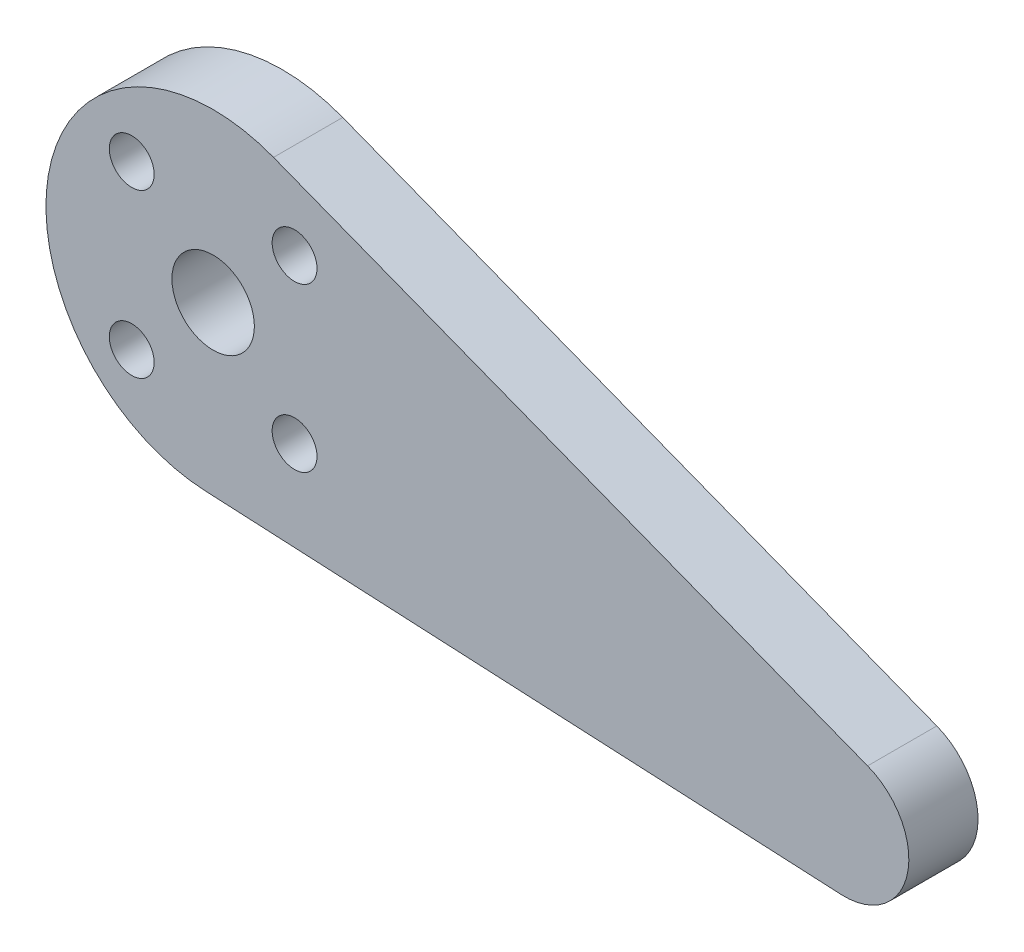
SolidWorks part; units mm, degrees
ref_plane "Front Plane" through (0, 0, 0) normal (0, 0, 1) x (1, 0, 0)
ref_plane "Top Plane" through (0, 0, 0) normal (0, 1, 0) x (1, 0, 0)
ref_plane "Right Plane" through (0, 0, 0) normal (1, 0, 0) x (0, 0, -1)
ref_plane "Plane1" through (0, 0, 0) normal (0, 0, -1) x (-1, 0, 0)
sketch "Sketch1" plane through (0, 0, 0) normal (0, 0, -1) x (-1, 0, 0)
  line L0 (-54.9006, 0.2614) -> (-46.1167, 9.6815) construction
  line L1 (-54.6285, -5.2121) -> (-0.5934, -2.5259)
  line L3 (-54.9006, 0.2614) -> (-1.2984, 11.6566) construction
  line L4 (-8.3993, 23.9536) -> (-43.781, 5.2606)
  line L5 (-46.7655, 4.7237) -> (-54.1894, 5.6953)
  circle A0 centre (-46.1167, 9.6815) radius 4 construction
  arc A2 (-54.1894, 5.6953) -> (-54.6285, -5.2121) centre (-54.9006, 0.2614) ccw
  arc A3 (-0.5934, -2.5259) -> (-8.3993, 23.9536) centre (-1.2984, 11.6566) ccw
  arc A4 (-46.7655, 4.7237) -> (-43.781, 5.2606) centre (-46.1167, 9.6815) ccw
  dimension "D2" = 14.2
  dimension "D3" = 12.88
  dimension "D5" = 35
  dimension "D6" = 8
  dimension "D7" = 10
  dimension "D1" = 54.8
extrude "Boss-Extrude1" add sketch "Sketch1" against normal blind 15
sketch "Sketch10" plane through (0, 0, 0) normal (0, 0, -1) x (-1, 0, 0)
  circle A0 centre (-1.2984, 11.6566) radius 14.2
  arc A1 (-0.5934, -2.5259) -> (-8.3993, 23.9536) centre (-1.2984, 11.6566) ccw construction
  circle A2 centre (-54.9006, 0.2614) radius 5.4803
  arc A3 (-54.1894, 5.6953) -> (-54.6285, -5.2121) centre (-54.9006, 0.2614) ccw construction
  point P5 (-1.2984, 11.6566)
hole_wizard "CBORE for M6 Hex Head Bolt1" positions "Sketch7" profile "Sketch6" counterbore size "M6" standard "Ansi Metric" end condition through all
sketch "Sketch7" plane through (0, 0, 0) normal (0, 0, -1) x (-1, 0, 0)
  point P0 (-1.2984, 11.6566)
sketch "Sketch6" plane through (1.2984, 11.6566, 0) normal (1, 0, 0) x (0, 1, 0)
  line L0 (0, 0) -> (0, 15)
  line L1 (0, 15) -> (3.5, 15)
  line L3 (3.5, 15) -> (3.5, 3)
  line L4 (3.5, 3) -> (12.8, 3)
  line L5 (12.8, 3) -> (12.8, 0)
  line L7 (12.8, 0) -> (0, 0)
  line L11 (0, -6.35) -> (0, 107.95) construction
  dimension "Thru Hole Dia." = 7
  dimension "Thru Hole Depth" = 15
  dimension "C'Bore Dia." = 25.6
  dimension "C'Bore Depth" = 3
ref_plane "Plane4" through (0, 0, 7.5) normal (0, 0, -1) x (-1, 0, 0)
sketch "Sketch30" plane through (0, 0, 15) normal (0, 0, 1) x (1, 0, 0)
  line L1 (68.7065, -22.2417) -> (-19.1857, -22.2417)
  line L2 (68.7065, -22.2417) -> (68.7065, 41.145)
  line L3 (68.7065, 41.145) -> (-19.1857, 41.145)
  line L4 (-19.1857, -22.2417) -> (-19.1857, 41.145)
extrude "Cut-Extrude8" cut sketch "Sketch30" against normal blind 0.125
sketch "Sketch31" plane through (0, 0, 0) normal (0, 0, -1) x (-1, 0, 0)
  line L1 (-64.611, 30.1264) -> (17.734, 30.1264)
  line L2 (-64.611, 30.1264) -> (-64.611, -8.8981)
  line L3 (-64.611, -8.8981) -> (17.734, -8.8981)
  line L4 (17.734, 30.1264) -> (17.734, -8.8981)
extrude "Cut-Extrude9" cut sketch "Sketch31" against normal blind 0.125
sketch "Sketch38" plane through (0, 0, 14.875) normal (0, 0, 1) x (1, 0, 0)
  circle A0 centre (1.2984, 11.6566) radius 3.5 construction
  circle A1 centre (1.2984, 11.6566) radius 3.5
  circle A2 centre (-5.616, 18.5718) radius 1.905
  circle A3 centre (8.2136, 18.571) radius 1.905
  circle A4 centre (8.2128, 4.7414) radius 1.905
  circle A5 centre (-5.6168, 4.7422) radius 1.905
  line B0 (3.7785, 13.3445) -> (3.7783, 9.9684)
  line B1 (-14.7035, 12.2926) -> (-1.6336, 12.2918)
  line B2 (-14.7033, 16.4201) -> (-14.7035, 12.2926)
  line B3 (-11.9069, 16.4199) -> (-14.7033, 16.4201)
  line B4 (-11.2749, 6.8948) -> (-11.2749, 6.8267)
  line B5 (-14.7039, 6.8951) -> (-11.2749, 6.8948)
  line B6 (-14.7036, 11.0226) -> (-14.7039, 6.8951)
  line B7 (-1.6336, 11.0218) -> (-14.7036, 11.0226)
  arc B8 (2.6475, 8.977) -> (3.7783, 9.9684) centre (2.7783, 9.9684) ccw
  arc B9 (3.7785, 13.3445) -> (2.6478, 14.336) centre (2.7785, 13.3446) ccw
  arc B10 (2.6478, 14.336) -> (-1.6336, 12.2918) centre (1.2984, 11.6566) ccw
  arc B11 (-11.9069, 16.4199) -> (-8.9599, 19.0076) centre (-11.9068, 19.3917) ccw
  arc B12 (-4.0299, 21.5478) -> (-8.9599, 19.0076) centre (-5.616, 18.5718) ccw
  arc B13 (-4.0299, 21.5478) -> (-1.7731, 21.3412) centre (-2.6561, 24.1255) ccw
  arc B14 (4.3711, 21.3408) -> (-1.7731, 21.3412) centre (1.2984, 11.6566) ccw
  arc B15 (4.3711, 21.3408) -> (6.628, 21.5471) centre (5.2545, 24.1251) ccw
  arc B16 (11.1896, 16.985) -> (6.628, 21.5471) centre (8.2136, 18.571) ccw
  arc B17 (11.1896, 16.985) -> (10.983, 14.7281) centre (13.7674, 15.6111) ccw
  arc B18 (10.9827, 8.5839) -> (10.983, 14.7281) centre (1.2984, 11.6566) ccw
  arc B19 (10.9827, 8.5839) -> (11.189, 6.3271) centre (13.7669, 7.7006) ccw
  arc B20 (6.6268, 1.7654) -> (11.189, 6.3271) centre (8.2128, 4.7414) ccw
  arc B21 (6.6268, 1.7654) -> (4.3699, 1.972) centre (5.253, -0.8123) ccw
  arc B22 (-1.7742, 1.9724) -> (4.3699, 1.972) centre (1.2984, 11.6566) ccw
  arc B23 (-1.7742, 1.9724) -> (-4.0311, 1.7661) centre (-2.6576, -0.8119) ccw
  arc B24 (-8.9608, 4.3068) -> (-4.0311, 1.7661) centre (-5.6168, 4.7422) ccw
  arc B25 (-8.9608, 4.3068) -> (-11.2749, 6.8267) centre (-11.9077, 3.9231) ccw
  arc B26 (-1.6336, 11.0218) -> (2.6475, 8.977) centre (1.2984, 11.6566) ccw
  dimension "D1" = 3.81
sketch_block_instance "Block1-1"
sketch_block "Block1"
extrude "Cut-Extrude10" cut sketch "Sketch38" against normal through all contours A2 | A3 | A4 | A5
sketch "Sketch39" plane through (0, 0, 0.125) normal (0, 0, -1) x (-1, 0, 0)
  circle A1 centre (-1.2984, 11.6566) radius 12.8 construction
  circle A2 centre (-1.2984, 11.6566) radius 12.8
extrude "Cut-Extrude11" cut sketch "Sketch39" against normal offset from surface (7.75 mm away) 7 flip side to cut contours A2 up to face at (-3.7118, 4.7422, 14.875)
sketch "Sketch40" plane through (0, 0, 14.875) normal (0, 0, 1) x (1, 0, 0)
  circle A0 centre (1.2984, 11.6566) radius 13
  dimension "D1" = 26
extrude "Cut-Extrude12" cut sketch "Sketch40" against normal offset from surface (6 mm away) 1 up to face at (32.9108, 6.1436, 7.875)
sketch "Sketch42" plane through (0, 0, 14.875) normal (0, 0, 1) x (1, 0, 0)
  line L0 (6.4237, 24.8994) -> (56.8786, 5.3722)
  line L3 (43.781, 5.2606) -> (8.3993, 23.9536)
  line L4 (0.5934, -2.5259) -> (54.6285, -5.2121)
  line L5 (54.1894, 5.6953) -> (46.7655, 4.7237)
  line L6 (43.781, 5.2606) -> (8.3993, 23.9536)
  line L8 (54.1894, 5.6953) -> (46.7655, 4.7237)
  arc A0 (54.6285, -5.2121) -> (54.1894, 5.6953) centre (54.9006, 0.2614) ccw construction
  arc A3 (8.3993, 23.9536) -> (0.5934, -2.5259) centre (1.2984, 11.6566) ccw
  arc A4 (54.6285, -5.2121) -> (54.1894, 5.6953) centre (54.9006, 0.2614) ccw
  arc A5 (43.781, 5.2606) -> (46.7655, 4.7237) centre (46.1167, 9.6815) ccw
  arc A6 (8.3993, 23.9536) -> (6.4237, 24.8994) centre (1.2984, 11.6566) ccw
  arc A7 (56.8786, 5.3722) -> (54.1894, 5.6953) centre (54.9006, 0.2614) ccw
  arc A8 (43.781, 5.2606) -> (46.7655, 4.7237) centre (46.1167, 9.6815) ccw
  point P10 (57.2562, 5.2095)
  point P12 (6.2267, 24.9756)
  point P13 (2.733, 26.3278)
  point P14 (56.8786, 5.3722)
  point P18 (56.8786, 5.2606)
  point P19 (56.8786, 5.3722)
  dimension "D1" = 0
extrude "Boss-Extrude2" add sketch "Sketch42" against normal up to surface (7 mm away) up to face at (32.9108, 6.1436, 7.875)
sketch "Sketch43" plane through (0, 0, 7.875) normal (0, 0, -1) x (-1, 0, 0)
  line L2 (-6.4237, 24.8994) -> (-56.8786, 5.3722)
  line L3 (-54.6285, -5.2121) -> (-0.5934, -2.5259)
  line L4 (-6.4237, 24.8994) -> (-56.8786, 5.3722)
  line L5 (-54.6285, -5.2121) -> (-0.5934, -2.5259)
  circle A0 centre (-1.2984, 11.6566) radius 12.8 construction
  circle A1 centre (-1.2984, 11.6566) radius 12.8
  arc A2 (-0.5934, -2.5259) -> (-6.4237, 24.8994) centre (-1.2984, 11.6566) ccw
  arc A3 (-56.8786, 5.3722) -> (-54.6285, -5.2121) centre (-54.9006, 0.2614) ccw
  arc A4 (-0.5934, -2.5259) -> (-6.4237, 24.8994) centre (-1.2984, 11.6566) ccw
  arc A5 (-56.8786, 5.3722) -> (-54.6285, -5.2121) centre (-54.9006, 0.2614) ccw
  dimension "D1" = 0
extrude "Boss-Extrude4" add sketch "Sketch43" along normal up to surface (4.875 mm away) up to face at (-3.7118, 4.7422, 3)
sketch "Sketch45" plane through (0, 0, 14.875) normal (0, 0, 1) x (1, 0, 0)
  line L2 (56.8786, 5.3722) -> (6.4237, 24.8994)
  line L3 (0.5934, -2.5259) -> (54.6285, -5.2121)
  line L4 (56.8786, 5.3722) -> (6.4237, 24.8994)
  line L5 (0.5934, -2.5259) -> (54.6285, -5.2121)
  circle A0 centre (1.2984, 11.6566) radius 13 construction
  circle A1 centre (1.2984, 11.6566) radius 13
  arc A2 (54.6285, -5.2121) -> (56.8786, 5.3722) centre (54.9006, 0.2614) ccw
  arc A3 (6.4237, 24.8994) -> (0.5934, -2.5259) centre (1.2984, 11.6566) ccw
  arc A4 (54.6285, -5.2121) -> (56.8786, 5.3722) centre (54.9006, 0.2614) ccw
  arc A5 (6.4237, 24.8994) -> (0.5934, -2.5259) centre (1.2984, 11.6566) ccw
  dimension "D1" = 0
extrude "Cut-Extrude13" cut sketch "Sketch45" against normal up to surface (6 mm away) contours L4 A5 L5 A4 up to face at (14.2984, 11.6566, 8.875)
